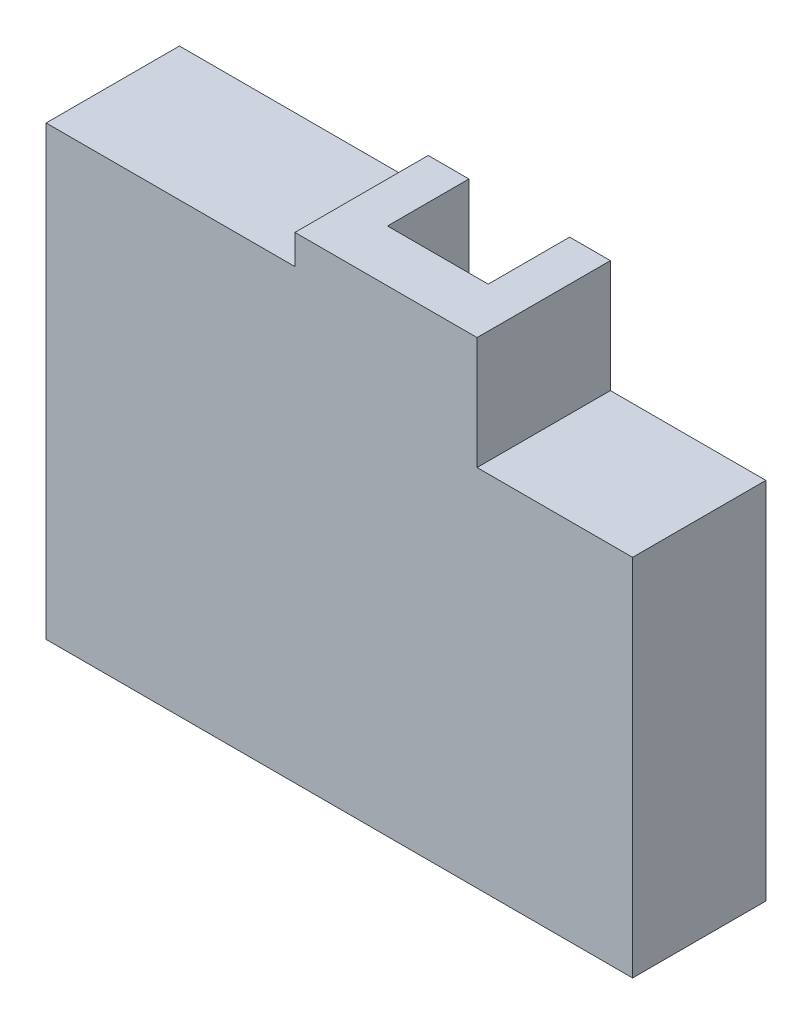
SolidWorks part; units mm, degrees
ref_plane "Front Plane" through (0, 0, 0) normal (0, 0, 1) x (1, 0, 0)
ref_plane "Top Plane" through (0, 0, 0) normal (0, 1, 0) x (1, 0, 0)
ref_plane "Right Plane" through (0, 0, 0) normal (1, 0, 0) x (0, 0, -1)
sketch "Sketch1" plane through (0, 0, 0) normal (0, 0, 1) x (1, 0, 0)
  line L0 (0, 0) -> (79.2, 0)
  line L1 (79.2, 0) -> (79.2, 49.2)
  line L2 (79.2, 49.2) -> (58.2, 49.2)
  line L3 (58.2, 49.2) -> (58.2, 64.4)
  line L4 (58.2, 64.4) -> (52.7, 64.4)
  line L5 (52.7, 64.4) -> (52.7, 61.4)
  line L6 (52.7, 61.4) -> (52.7, 29)
  line L7 (79.2, 0) -> (76.2, 0)
  line L8 (76.2, 0) -> (76.2, 49.2)
  line L9 (76.2, 49.2) -> (58.2, 49.2)
  line L10 (58.2, 49.2) -> (58.2, 29)
  line L11 (58.2, 29) -> (52.7, 29)
  line L12 (0, 0) -> (0, 3)
  line L13 (0, 3) -> (76.2, 3)
  line L14 (0, 0) -> (0, 60.4)
  line L15 (0, 60.4) -> (3, 60.4)
  line L16 (3, 60.4) -> (3, 3)
  line L17 (0, 60.4) -> (0, 57.4)
  line L18 (0, 57.4) -> (33.6, 57.4)
  line L19 (33.6, 57.4) -> (33.6, 60.4)
  line L20 (33.6, 60.4) -> (3, 60.4)
  line L21 (52.7, 64.4) -> (33.6, 64.4)
  line L22 (33.6, 64.4) -> (33.6, 60.4)
  line L23 (33.6, 57.4) -> (33.6, 29)
  line L24 (33.6, 29) -> (39.1, 29)
  line L25 (39.1, 29) -> (39.1, 64.4)
  line L26 (58.2, 61.4) -> (33.6, 61.4)
  line L27 (79.2, 49.2) -> (79.2, 46.2)
  line L28 (79.2, 46.2) -> (58.2, 46.2)
  line L29 (58.2, 46.2) -> (58.2, 49.2)
  dimension "D1" = 3
  dimension "D2" = 79.2
  dimension "D3" = 49.2
  dimension "D4" = 60.4
extrude "Boss-Extrude3" add sketch "Sketch1" along normal blind 3 contours L14 L18 L16 L15 | L18 L14 L13 L16 | L13 L12 L0 L8 | L8 L28 L10 L11 L6 L26 L25 L24 L23 L18 L16 L13 | L19 L20 L16 L18 | L25 L26 L22 L19 L23 L24 | L26 L25 L21 L22 | L26 L5 L21 L25 | L26 L3 L4 L5 | L3 L26 L6 L11 L10 | L28 L8 L2 L10 | L28 L1 L2 L8 | L1 L28 L8 L0 region at (38.1, 1.5, 0) region at (77.7, 23.1, 0) region at (1.5, 30.2, 0) region at (37.5589, 28.2618, 0) region at (1.5, 58.9, 0) region at (77.7, 47.7, 0) region at (67.2, 47.7, 0) region at (18.3, 58.9, 0) region at (55.45, 45.2, 0) region at (36.35, 45.2, 0) region at (55.45, 62.9, 0) region at (36.35, 62.9, 0) region at (45.9, 62.9, 0)
extrude "Boss-Extrude4" add sketch "Sketch1<9>" against normal blind 15 contours L25 L26 L22 L19 L23 L24 | L26 L25 L21 L22 | L26 L5 L21 L25 | L26 L3 L4 L5 | L3 L26 L6 L11 L10 | L28 L8 L2 L10 | L28 L1 L2 L8 | L1 L28 L8 L0 | L13 L12 L0 L8 | L18 L14 L13 L16 | L19 L20 L16 L18 | L14 L18 L16 L15 region at (38.1, 1.5, 0) region at (77.7, 23.1, 0) region at (1.5, 30.2, 0) region at (1.5, 58.9, 0) region at (77.7, 47.7, 0) region at (67.2, 47.7, 0) region at (18.3, 58.9, 0) region at (55.45, 45.2, 0) region at (36.35, 45.2, 0) region at (55.45, 62.9, 0) region at (36.35, 62.9, 0) region at (45.9, 62.9, 0)
sketch "Sketch1<9>" plane through (0, 0, 0) normal (0, 0, 1) x (1, 0, 0) same geometry as "Sketch1"
sketch "Sketch2" plane through (0, 0, 0) normal (0, -1, 0) x (-1, 0, 0)
  line L0 (0, 15) -> (-33.6, 15)
  line L1 (0, 15) -> (0, 0)
  line L2 (0, 0) -> (-33.6, 0)
  line L3 (-33.6, 0) -> (-33.6, 15)
  line L4 (-33.6, 15) -> (-18.6, 0)
  line M5 (0, -3) -> (0, 15)
  line M6 (0, 15) -> (-79.2, 15)
extrude "Cut-Extrude1" cut sketch "Sketch2" against normal blind 3 contours L4 L2 M6 M5 region at (13.4092, 0, -8.2184)
sketch "Sketch3" plane through (0, 0, 0) normal (-1, 0, 0) x (0, 0, 1)
  line L0 (0, 3) -> (-15, 18)
  line L1 (-15, 3) -> (-15, 60.4) construction
  line L2 (-15, 18) -> (-15, 3)
  line L3 (-15, 3) -> (0, 3)
extrude "Cut-Extrude2" cut sketch "Sketch3" against normal blind 3
sketch "Sketch4" plane through (0, 64.4, 0) normal (0, 1, 0) x (1, 0, 0)
  line L0 (58.2, 15) -> (52.7, 15)
  line L1 (58.2, 15) -> (33.6, 15) construction
  line L2 (52.7, 15) -> (52.7, 4)
  line L3 (33.6, 15) -> (39.1, 15)
  line L4 (39.1, 15) -> (39.1, 4)
  line L5 (39.1, 4) -> (53.0577, 4)
  line L6 (39.1, 15) -> (52.7, 15)
  line M2 (58.2, 15) -> (33.6, 15)
extrude "Cut-Extrude3" cut sketch "Sketch4" against normal blind 3 contours L4 L5 L2 M2 region at (45.9, 64.4, -9.5)
sketch "Sketch5" plane through (0, 0, 0) normal (0, -1, 0) x (-1, 0, 0)
  line L0 (-79.2, 15) -> (-51.6, 15)
  line L1 (-33.6, 15) -> (-79.2, 15) construction
  line L2 (-51.6, 15) -> (-36.6, 0)
  line L3 (-36.6, 0) -> (-18.6, 0)
  line L4 (-18.6, 0) -> (-33.6, 15)
  line L5 (-33.6, 15) -> (-51.6, 15)
  line M6 (-18.6, 0) -> (-33.6, 15)
  line M7 (-33.6, 15) -> (-79.2, 15)
extrude "Cut-Extrude4" cut sketch "Sketch5" against normal blind 3 contours L2 L3 M6 M7 region at (35.1, 0, -7.5)
